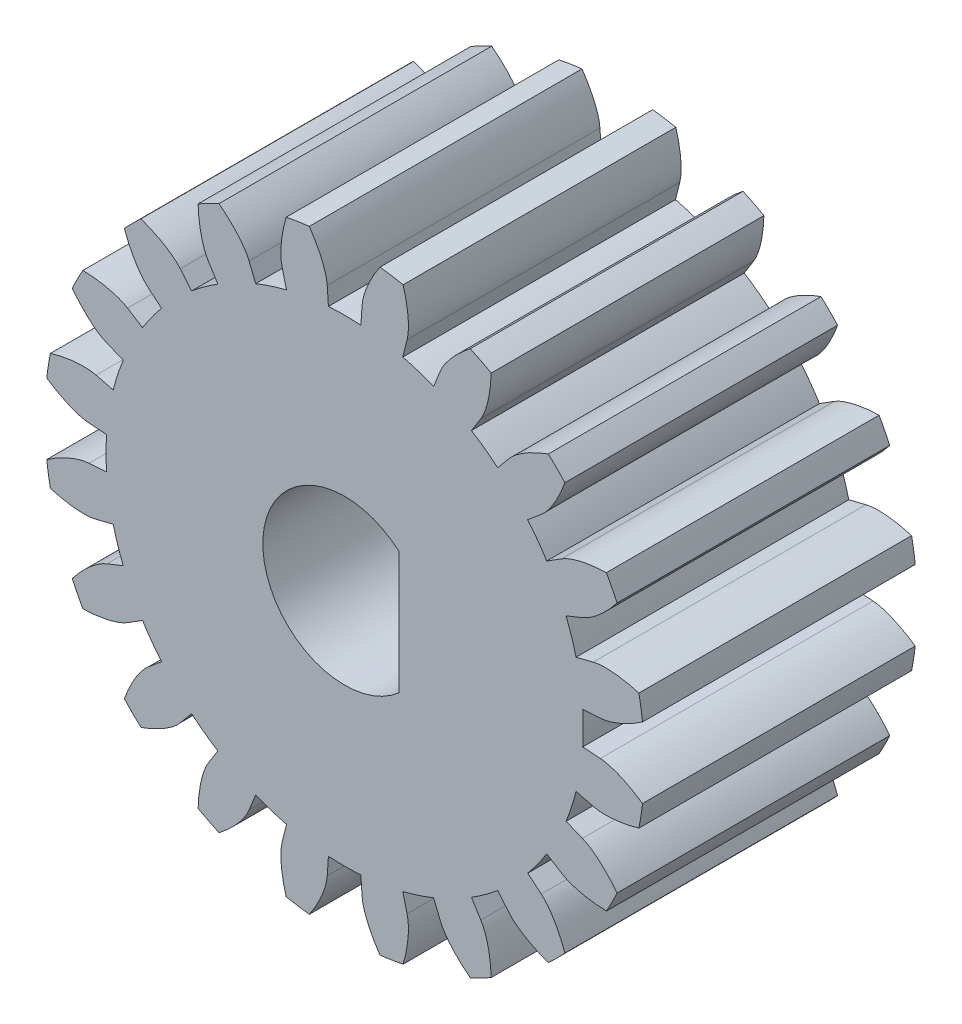
SolidWorks part; units mm, degrees
ref_plane "前视基准面" through (0, 0, 0) normal (0, 0, 1) x (1, 0, 0)
ref_plane "上视基准面" through (0, 0, 0) normal (0, 1, 0) x (1, 0, 0)
ref_plane "右视基准面" through (0, 0, 0) normal (1, 0, 0) x (0, 0, -1)
other "Configuration Table"
sketch "草图1" plane through (0, 0, 0) normal (0, 0, 1) x (1, 0, 0)
  line L0 (0, 0) -> (5, 0) construction
  line L1 (0, 0) -> (4.9846, 0.3923) construction
  line L2 (0, 0) -> (4.6876, 0.3194)
  line L3 (4.9846, 0.3923) -> (4.9846, -0.3923) construction
  line L4 (0, 0) -> (4.6876, -0.3194)
  circle A0 centre (0, 0) radius 5.5
  circle A1 centre (0, 0) radius 5 construction
  circle A2 centre (0, 0) radius 4.375
  circle A3 centre (0, 0) radius 4.6985 construction
  circle A4 centre (0, 0) radius 1.475
  spline S0 degree 4 poles (4.6876, 0.3194) (4.7233, 0.3218) (4.8225, 0.336) (5.0062, 0.3926) (5.2885, 0.5242) (5.6241, 0.7499) (6.0094, 1.0976) (6.395, 1.5688) (6.7398, 2.1414) (7.0933, 2.9696) (7.3065, 3.8467) (7.3947, 4.7795) (7.347, 5.8934) (7.1568, 6.9938) (6.7515, 8.227) (6.0949, 9.5107) (5.2611, 10.6861) (4.2765, 11.7378) (3.1662, 12.6551) (1.9531, 13.4307) (0.6586, 14.0604) (-0.5283, 14.4821) (-1.4854, 14.7287) (-2.1912, 14.8654) (-2.6338, 14.9356) (-2.9917, 14.9827) (-3.3451, 15.0208) (-3.7095, 15.05) (-4.0266, 15.0684) (-4.3306, 15.0786) (-4.6986, 15.0842) (-4.9527, 15.0816) (-5.4001, 15.0704) (-5.6957, 15.0494) (-6.0237, 15.027) (-6.2862, 14.9991) (-6.5922, 14.9657) (-6.7961, 14.9366) (-6.9439, 14.9154) (-7.0152, 14.9043) knots 0 0 0 0 0 0.005604 0.015718 0.02996 0.048734 0.068727 0.096889 0.125051 0.153212 0.209535 0.237696 0.271429 0.327752 0.384075 0.440398 0.496721 0.553044 0.609367 0.66569 0.722013 0.778336 0.806497 0.820578 0.834659 0.84874 0.86282 0.876901 0.890982 0.900036 0.909091 0.931818 0.943182 0.954545 0.965909 0.977273 0.988636 1 1 1 1 1 construction
  spline S1 degree 4 poles (4.6876, 0.3194) (4.7233, 0.3218) (4.8225, 0.336) (5.0062, 0.3926) (5.2885, 0.5242) (5.6241, 0.7499) (6.0094, 1.0976) (6.395, 1.5688) (6.7398, 2.1414) (7.0933, 2.9696) (7.3065, 3.8467) (7.3947, 4.7795) (7.347, 5.8934) (7.1568, 6.9938) (6.7515, 8.227) (6.0949, 9.5107) (5.2611, 10.6861) (4.2765, 11.7378) (3.1662, 12.6551) (1.9531, 13.4307) (0.6586, 14.0604) (-0.5283, 14.4821) (-1.4854, 14.7287) (-2.1912, 14.8654) (-2.6338, 14.9356) (-2.9917, 14.9827) (-3.3451, 15.0208) (-3.7095, 15.05) (-4.0266, 15.0684) (-4.3306, 15.0786) (-4.5463, 15.0819) (-4.6529, 15.0825) (-4.7054, 15.0825) knots 0 0 0 0 0 0.005604 0.015718 0.02996 0.048734 0.068727 0.096889 0.125051 0.153212 0.209535 0.237696 0.271429 0.327752 0.384075 0.440398 0.496721 0.553044 0.609367 0.66569 0.722013 0.778336 0.806497 0.820578 0.834659 0.84874 0.86282 0.876901 0.890982 0.900036 0.909091 0.909091 0.909091 0.909091 0.909091
  spline S2 degree 4 poles (4.6876, -0.3194) (4.7233, -0.3218) (4.8225, -0.336) (5.0062, -0.3926) (5.2885, -0.5242) (5.6241, -0.7499) (6.0094, -1.0976) (6.395, -1.5688) (6.7398, -2.1414) (7.0933, -2.9696) (7.3065, -3.8467) (7.3947, -4.7795) (7.347, -5.8934) (7.1568, -6.9938) (6.7515, -8.227) (6.0949, -9.5107) (5.2611, -10.6861) (4.2765, -11.7378) (3.1662, -12.6551) (1.9531, -13.4307) (0.6586, -14.0604) (-0.5283, -14.4821) (-1.4854, -14.7287) (-2.1912, -14.8654) (-2.6338, -14.9356) (-2.9917, -14.9827) (-3.3451, -15.0208) (-3.7095, -15.05) (-4.0266, -15.0684) (-4.3306, -15.0786) (-4.6986, -15.0842) (-4.9527, -15.0816) (-5.4001, -15.0704) (-5.6957, -15.0494) (-6.0237, -15.027) (-6.2862, -14.9991) (-6.5922, -14.9657) (-6.7961, -14.9366) (-6.9439, -14.9154) (-7.0152, -14.9043) knots 0 0 0 0 0 0.005604 0.015718 0.02996 0.048734 0.068727 0.096889 0.125051 0.153212 0.209535 0.237696 0.271429 0.327752 0.384075 0.440398 0.496721 0.553044 0.609367 0.66569 0.722013 0.778336 0.806497 0.820578 0.834659 0.84874 0.86282 0.876901 0.890982 0.900036 0.909091 0.931818 0.943182 0.954545 0.965909 0.977273 0.988636 1 1 1 1 1 construction
  spline S3 degree 4 poles (4.6876, -0.3194) (4.7233, -0.3218) (4.8225, -0.336) (5.0062, -0.3926) (5.2885, -0.5242) (5.6241, -0.7499) (6.0094, -1.0976) (6.395, -1.5688) (6.7398, -2.1414) (7.0933, -2.9696) (7.3065, -3.8467) (7.3947, -4.7795) (7.347, -5.8934) (7.1568, -6.9938) (6.7515, -8.227) (6.0949, -9.5107) (5.2611, -10.6861) (4.2765, -11.7378) (3.1662, -12.6551) (1.9531, -13.4307) (0.6586, -14.0604) (-0.5283, -14.4821) (-1.4854, -14.7287) (-2.1912, -14.8654) (-2.6338, -14.9356) (-2.9917, -14.9827) (-3.3451, -15.0208) (-3.7095, -15.05) (-4.0266, -15.0684) (-4.3306, -15.0786) (-4.5463, -15.0819) (-4.6529, -15.0825) (-4.7054, -15.0825) knots 0 0 0 0 0 0.005604 0.015718 0.02996 0.048734 0.068727 0.096889 0.125051 0.153212 0.209535 0.237696 0.271429 0.327752 0.384075 0.440398 0.496721 0.553044 0.609367 0.66569 0.722013 0.778336 0.806497 0.820578 0.834659 0.84874 0.86282 0.876901 0.890982 0.900036 0.909091 0.909091 0.909091 0.909091 0.909091
  point P15 (4.9846, 0)
  dimension "齿顶圆直径" = 11
  dimension "分度圆直径" = 10
  dimension "齿根圆直径" = 8.75
  dimension "基圆直径" = 9.3969
  dimension "内孔直径" = 2.95
  dimension "渐近线镜像线夹角" = 4.5
extrude "凸台-拉伸1" add sketch "草图1" along normal blind 5 contours A0 | A4
extrude "切除-拉伸1" cut sketch "草图1<3>" along normal through all contours A2 S3 A0 S1 region at (5.0102, 0, 0)
sketch "草图1<3>" plane through (0, 0, 0) normal (0, 0, 1) x (1, 0, 0) same geometry as "草图1"
pattern_circular "阵列(圆周)1" count 20 every 18 about axis through (0, 0, 5) along (0, 0, 1) of "切除-拉伸1"
sketch "草图2" plane through (0, 0, 5) normal (0, 0, 1) x (1, 0, 0)
  circle A0 centre (0, 0) radius 1.475
extrude "凸台-拉伸2" add sketch "草图2" against normal through all
sketch "草图3" plane through (0, 0, 5) normal (0, 0, 1) x (1, 0, 0)
  line L0 (1, 1.118) -> (1, -1.118)
  circle A0 centre (0, 0) radius 1.5
  dimension "D2" = 3
  dimension "D1" = 1
extrude "切除-拉伸2" cut sketch "草图3" against normal through all contours L0 A0 region at (-0.148, 0, 5)
equation "\"m\"= 0.5'模数"
equation "\"z\"= 20'齿数"
equation "\"a\"= 20度'压力角"
equation "\"d\"= \"m\" * \"z\"'分度圆直径"
equation "\"da\"= ( \"z\" + 2 ) * \"m\"'齿顶圆直径"
equation "\"df\"= ( \"z\" - 2.5 ) * \"m\"'齿根圆直径"
equation "\"s\"= 0.5 * PI * \"m\"'分度圆齿厚"
equation "\"r\"= 0.38 * \"m\"'齿根圆角"
equation "\"B\"= 0.3 * \"d\"'齿厚"
equation "\"db\"= \"m\" * \"z\" * cos ( \"a\" )'基圆直径"
equation "\"rb\"= \"db\" / 2'基圆半径"
equation "\"齿顶圆直径@草图1\"= \"da\""
equation "\"分度圆直径@草图1\"= \"d\""
equation "\"齿根圆直径@草图1\"= \"df\""
equation "\"基圆直径@草图1\"= \"db\""
equation "\"渐近线镜像线夹角@草图1\"= 360 / 4 / \"z\""
equation "\"h\"= 5'齿轮厚度"
equation "\"ir\"= 2.95'内孔直径"
equation "\"内孔直径@草图1\"= \"ir\""
equation "\"齿轮厚@凸台-拉伸1\"= \"h\""
equation "\"齿轮夹角@阵列(圆周)1\"= 360 / \"z\""
equation "\"齿数@阵列(圆周)1\"= \"z\""
